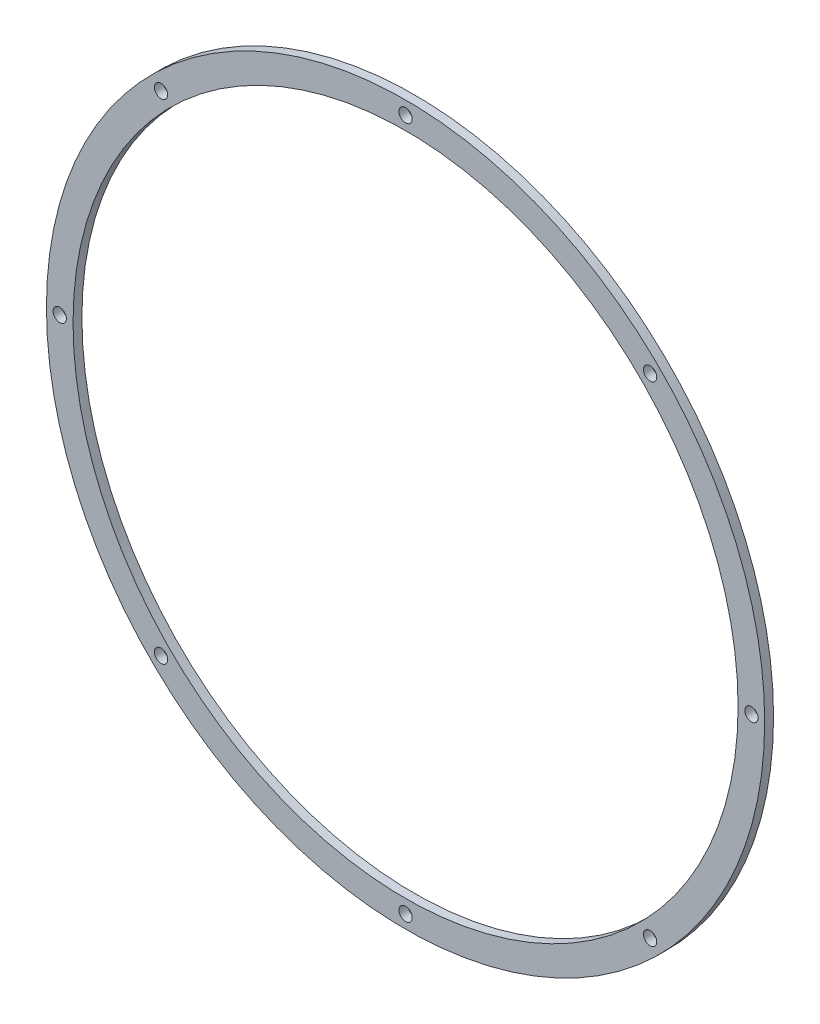
SolidWorks part; units mm, degrees
ref_plane "Płaszczyzna przednia" through (0, 0, 0) normal (0, 0, 1) x (1, 0, 0)
ref_plane "Płaszczyzna górna" through (0, 0, 0) normal (0, 1, 0) x (1, 0, 0)
ref_plane "Płaszczyzna prawa" through (0, 0, 0) normal (1, 0, 0) x (0, 0, -1)
sketch "Szkic1" plane through (0, 0, 0) normal (0, 0, 1) x (1, 0, 0)
  circle A0 centre (0, 0) radius 81
  circle A1 centre (0, 0) radius 75
  dimension "D1" = 162
  dimension "D2" = 150
extrude "Dodanie-wyciągnięcie1" add sketch "Szkic1" along normal blind 2
sketch "Szkic2" plane through (0, 0, 2) normal (0, 0, 1) x (1, 0, 0)
  circle A0 centre (0, 78) radius 1.5
  circle A1 centre (0, 0) radius 75 construction
  circle A2 centre (0, 0) radius 81 construction
  circle A3 centre (0, 0) radius 81 construction
  circle A4 centre (0, 0) radius 75 construction
  dimension "D1" = 3
  dimension "D2" = 162
  dimension "D3" = 78
extrude "Wytnij-wyciągnięcie1" cut sketch "Szkic2" against normal up to surface (2 mm away) up to face at (81, 0, 0)
pattern_circular "Szyk kołowy1" count 8 over 360 about axis through (0, 0, 2) along (0, 0, -1) of "Wytnij-wyciągnięcie1"
equation "\"D3@Szkic2\"=\"D2@Szkic2\"/2-3"
